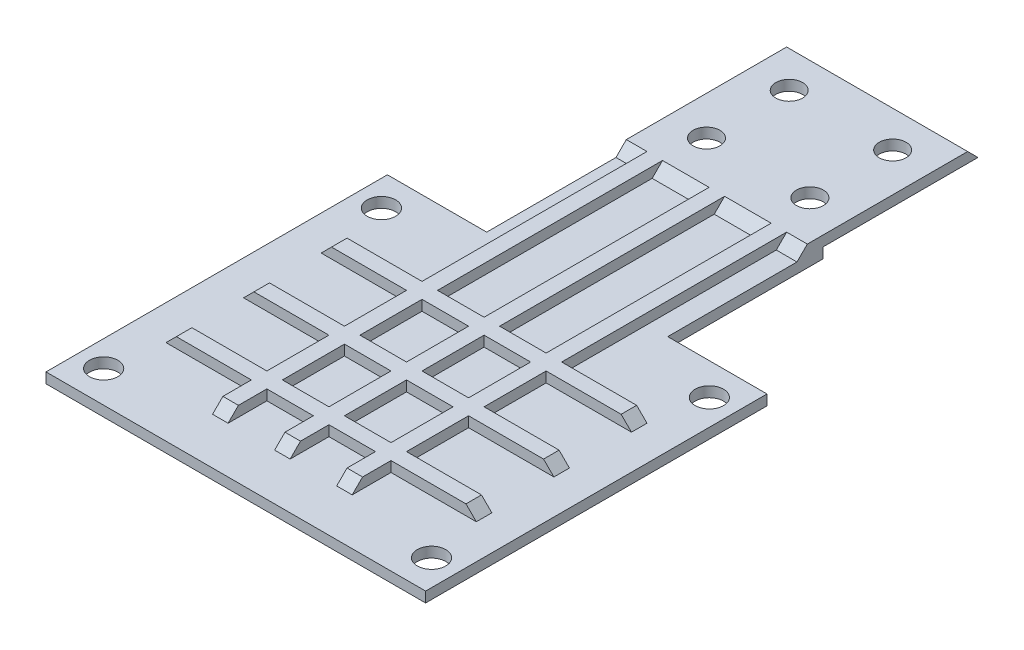
SolidWorks part; units mm, degrees
ref_plane "Front Plane" through (0, 0, 0) normal (0, 0, 1) x (1, 0, 0)
ref_plane "Top Plane" through (0, 0, 0) normal (0, 1, 0) x (1, 0, 0)
ref_plane "Right Plane" through (0, 0, 0) normal (1, 0, 0) x (0, 0, -1)
sketch "Sketch1" plane through (0, 0, 0) normal (0, 1, 0) x (1, 0, 0)
  line L0 (0, -76) -> (0, 76) construction
  line L5 (-17.5, 42.995) -> (-17.5, -42.995)
  line L6 (-31.7, -102.855) -> (31.7, -102.855) construction
  line L11 (-31.7, -102.855) -> (-31.7, -49.145) construction
  line L12 (-31.7, -49.145) -> (31.7, -49.145) construction
  line L13 (31.7, -102.855) -> (31.7, -49.145) construction
  line L14 (0, -49.145) -> (0, -102.855) construction
  line L15 (-31.7, -76) -> (31.7, -76) construction
  line L16 (-31.7, 49.145) -> (31.7, 49.145) construction
  line L17 (-31.7, 49.145) -> (-31.7, 102.855) construction
  line L18 (-31.7, 102.855) -> (31.7, 102.855) construction
  line L19 (31.7, 49.145) -> (31.7, 102.855) construction
  line L20 (0, 102.855) -> (0, 49.145) construction
  line L21 (-31.7, 76) -> (31.7, 76) construction
  line L22 (-36.7, -42.995) -> (-17.5, -42.995)
  line L23 (-36.7, -42.995) -> (-36.7, -109.005)
  line L24 (-36.7, -109.005) -> (36.7, -109.005)
  line L25 (36.7, -42.995) -> (36.7, -109.005)
  line L26 (0, -109.005) -> (0, -32.2076) construction
  line L27 (-36.7, -76) -> (36.7, -76) construction
  line L28 (-36.7, 42.995) -> (-17.5, 42.995)
  line L29 (-36.7, 42.995) -> (-36.7, 109.005)
  line L30 (-36.7, 109.005) -> (36.7, 109.005)
  line L31 (36.7, 42.995) -> (36.7, 109.005)
  line L32 (0, 109.005) -> (0, 37.2379) construction
  line L33 (-36.7, 76) -> (36.7, 76) construction
  line L34 (17.5, -42.995) -> (17.5, 42.995)
  line L35 (17.5, 42.995) -> (36.7, 42.995)
  line L36 (17.5, -42.995) -> (36.7, -42.995)
  circle A4 centre (-31.7, 102.855) radius 2.75
  circle A5 centre (-31.7, 49.145) radius 2.75
  circle A6 centre (31.7, 49.145) radius 2.75
  circle A7 centre (31.7, 102.855) radius 2.75
  circle A8 centre (31.7, -102.855) radius 2.75
  circle A9 centre (31.7, -49.145) radius 2.75
  circle A10 centre (-31.7, -49.145) radius 2.75
  circle A11 centre (-31.7, -102.855) radius 2.75
  point P2 (0, 0)
  point P93 (0, -76)
  point P121 (0, 76)
  point P131 (0, 76)
  point P202 (0, -76)
  dimension "D5" = 5.5
  dimension "D6" = 5.5
  dimension "D7" = 5.5
  dimension "D8" = 5.5
  dimension "D9" = 5.5
  dimension "D10" = 5.5
  dimension "D11" = 5.5
  dimension "D12" = 5.5
  dimension "D1" = 152
  dimension "D2" = 63.4
  dimension "D3" = 53.71
  dimension "D4" = 53.71
  dimension "D13" = 73.4
  dimension "D14" = 66.01
  dimension "D15" = 66.01
  dimension "D16" = 35
extrude "Boss-Extrude1" add sketch "Sketch1" along normal blind 2
sketch "Sketch2" plane through (0, 2, 0) normal (0, 1, 0) x (1, 0, 0)
  line L5 (13.5, 0) -> (10.5, 0)
  line L6 (13.5, 0) -> (13.5, -100)
  line L11 (13.5, -100) -> (10.5, -100)
  line L12 (10.5, 0) -> (10.5, -100)
  line L17 (12, -100) -> (12, 0) construction
  line L18 (13.5, -50) -> (10.5, -50) construction
  line L19 (1.5, 0) -> (-1.5, 0)
  line L20 (1.5, 0) -> (1.5, -100)
  line L21 (1.5, -100) -> (-1.5, -100)
  line L22 (-1.5, 0) -> (-1.5, -100)
  line L23 (0, -100) -> (0, 0) construction
  line L24 (1.5, -50) -> (-1.5, -50) construction
  line L25 (-10.5, 0) -> (-13.5, 0)
  line L26 (-10.5, 0) -> (-10.5, -100)
  line L27 (-10.5, -100) -> (-13.5, -100)
  line L28 (-13.5, 0) -> (-13.5, -100)
  line L29 (-12, -100) -> (-12, 0) construction
  line L30 (-10.5, -50) -> (-13.5, -50) construction
  point P81 (12, -50)
  point P103 (-12, -50)
  point P117 (0, -50)
  dimension "D1" = 3
  dimension "D2" = 3
  dimension "D3" = 3
  dimension "D4" = 100
  dimension "D5" = 12
  dimension "D6" = 12
extrude "Boss-Extrude2" add sketch "Sketch2" along normal blind 2
sketch "Sketch3" plane through (0, 2, 0) normal (0, 1, 0) x (1, 0, 0)
  line L0 (-36.7, -76) -> (36.7, -76) construction
  line L1 (-36.7, -42.995) -> (-36.7, -109.005) construction
  line L2 (36.7, -109.005) -> (36.7, -42.995) construction
  line L4 (-30, -89.5) -> (30, -89.5)
  line L5 (-30, -89.5) -> (-30, -92.5)
  line L6 (-30, -92.5) -> (30, -92.5)
  line L7 (30, -89.5) -> (30, -92.5)
  line L8 (0, -92.5) -> (0, -89.5) construction
  line L9 (-30, -91) -> (30, -91) construction
  line L10 (-30, -59.5) -> (30, -59.5)
  line L11 (-30, -59.5) -> (-30, -62.5)
  line L12 (-30, -62.5) -> (30, -62.5)
  line L13 (30, -59.5) -> (30, -62.5)
  line L14 (0, -62.5) -> (0, -59.5) construction
  line L15 (-30, -61) -> (30, -61) construction
  line L16 (-30, -74.5) -> (30, -74.5)
  line L17 (-30, -74.5) -> (-30, -77.5)
  line L18 (-30, -77.5) -> (30, -77.5)
  line L19 (30, -74.5) -> (30, -77.5)
  line L20 (0, -77.5) -> (0, -74.5) construction
  line L21 (-30, -76) -> (30, -76) construction
  point P16 (0, -76)
  point P87 (0, -76)
  point P112 (0, -61)
  point P122 (0, -91)
  dimension "D1" = 3
  dimension "D2" = 3
  dimension "D3" = 15
  dimension "D4" = 15
  dimension "D5" = 3
  dimension "D6" = 60
extrude "Boss-Extrude3" add sketch "Sketch3" along normal up to surface (2 mm away) up to face at (0, 4, 50)
chamfer "Chamfer1" distance 2 9 edges at (30, 4, 61) (30, 4, 76) (30, 4, 91) (12, 4, 100) (0, 4, 100) (-12, 4, 100) (-30, 4, 91) (-30, 4, 76) (-30, 4, 61)
mirror "Mirror1" about plane through (0, 0, 0) normal (0, 0, 1) of "Chamfer1", "Boss-Extrude3", "Boss-Extrude2"
ref_plane "Plane1" through (0, 0, 0) normal (1, 0, 0) x (0, 0, -1)
sketch "Sketch5" plane through (0, 4, 0) normal (0, 1, 0) x (1, 0, 0)
  line L0 (17.5, -42.995) -> (17.5, 42.995) construction
  line L1 (17.5, -15) -> (-17.5, -15)
  line L2 (17.5, -15) -> (17.5, 15)
  line L3 (17.5, 15) -> (-17.5, 15)
  line L4 (-17.5, -15) -> (-17.5, 15)
  line L5 (0, 15) -> (0, -15) construction
  line L6 (17.5, 0) -> (-17.5, 0) construction
  line L7 (-17.5, 42.995) -> (-17.5, -42.995) construction
  line L8 (0, -1.1) -> (0, 1.1) construction
  point P88 (0, 0)
  dimension "D1" = 30
extrude "Boss-Extrude4" add sketch "Sketch5" against normal up to surface (2 mm away) up to face at (0, 2, 0)
chamfer "Chamfer2" distance 3 4 edges at (15.5, 2, 15) (6, 2, 15) (-6, 2, 15) (-15.5, 2, 15)
sketch "Sketch6" plane through (17.5, 0, 0) normal (1, 0, 0) x (0, 0, -1)
  line L0 (-13, 0) -> (-13, 2)
  line L1 (-42.995, 0) -> (42.995, 0) construction
  line L2 (-13, 2) -> (15, 2)
  line L3 (15, 2) -> (15, 4)
  line L4 (15, 4) -> (109.005, 4)
  line L5 (109.005, 4) -> (109.005, 0)
  line L6 (109.005, 0) -> (-13, 0)
  dimension "D1" = 28
extrude "Cut-Extrude1" cut sketch "Sketch6" against normal through all both and the other way through all
sketch "Sketch7" plane through (0, 4, 0) normal (0, 1, 0) x (1, 0, 0)
  line L0 (-17.5, -13) -> (17.5, -13) construction
  line L1 (-10, -8) -> (10, -8) construction
  line L2 (-10, -8) -> (-10, 8) construction
  line L3 (-10, 8) -> (10, 8) construction
  line L4 (10, -8) -> (10, 8) construction
  line L5 (0, 8) -> (0, -8) construction
  line L6 (-10, 0) -> (10, 0) construction
  circle A0 centre (-10, -8) radius 2.6
  circle A1 centre (-10, 8) radius 2.6
  circle A2 centre (10, 8) radius 2.6
  circle A3 centre (10, -8) radius 2.6
  point P300 (0, 0)
  dimension "D1" = 5.2
  dimension "D2" = 5.2
  dimension "D3" = 5.2
  dimension "D4" = 5.2
  dimension "D5" = 20
  dimension "D6" = 5
extrude "Cut-Extrude2" cut sketch "Sketch7" against normal through all both
sketch "Sketch8" plane through (17.5, 0, 0) normal (1, 0, 0) x (0, 0, -1)
  line L0 (15, 4) -> (17, 2)
  line L1 (17, 2) -> (15, 2)
  line L2 (15, 2) -> (15, 4)
  dimension "D1" = 45
extrude "Boss-Extrude5" add sketch "Sketch8" against normal up to surface (35 mm away) up to face at (-17.5, 2, 14.4988)
sketch "Sketch9" plane through (0, 4, 0) normal (0, 1, 0) x (1, 0, 0)
  line L0 (17.5, 15) -> (-17.5, 15) construction
  line L1 (-13.5, 15) -> (-10.5, 15)
  line L2 (-13.5, 15) -> (-13.5, 17)
  line L3 (-13.5, 17) -> (-10.5, 17)
  line L4 (-10.5, 15) -> (-10.5, 17)
  line L5 (-12, 17) -> (-12, 15) construction
  line L6 (-13.5, 16) -> (-10.5, 16) construction
  line L7 (-17.5, 17) -> (17.5, 17) construction
  line L8 (-10.5, -59.5) -> (-10.5, -16) construction
  line L9 (-1.5, 15) -> (1.5, 15)
  line L10 (-1.5, 15) -> (-1.5, 17)
  line L11 (-1.5, 17) -> (1.5, 17)
  line L12 (1.5, 15) -> (1.5, 17)
  line L13 (0, 17) -> (0, 15) construction
  line L14 (-1.5, 16) -> (1.5, 16) construction
  line L15 (10.5, 15) -> (13.5, 15)
  line L16 (10.5, 15) -> (10.5, 17)
  line L17 (10.5, 17) -> (13.5, 17)
  line L18 (13.5, 15) -> (13.5, 17)
  line L19 (12, 17) -> (12, 15) construction
  line L20 (10.5, 16) -> (13.5, 16) construction
  line L22 (-13.5, -18) -> (-13.5, -59.5) construction
  line L23 (-1.5, -16) -> (-1.5, -59.5) construction
  line L24 (1.5, -59.5) -> (1.5, -16) construction
  line L25 (10.5, -16) -> (10.5, -59.5) construction
  line L26 (13.5, -59.5) -> (13.5, -16) construction
  point P120 (12, 16)
  point P132 (0, 16)
  point P220 (-12, 16)
extrude "Cut-Extrude3" cut sketch "Sketch9" against normal through all both
equation "\"Reikä\"= 5.5"
equation "\"D5@Sketch1\"=\"Reikä\""
equation "\"D6@Sketch1\"=\"Reikä\""
equation "\"D7@Sketch1\"=\"Reikä\""
equation "\"D8@Sketch1\"=\"Reikä\""
equation "\"D9@Sketch1\"=\"Reikä\""
equation "\"D10@Sketch1\"=\"Reikä\""
equation "\"D11@Sketch1\"=\"Reikä\""
equation "\"D12@Sketch1\"=\"Reikä\""
